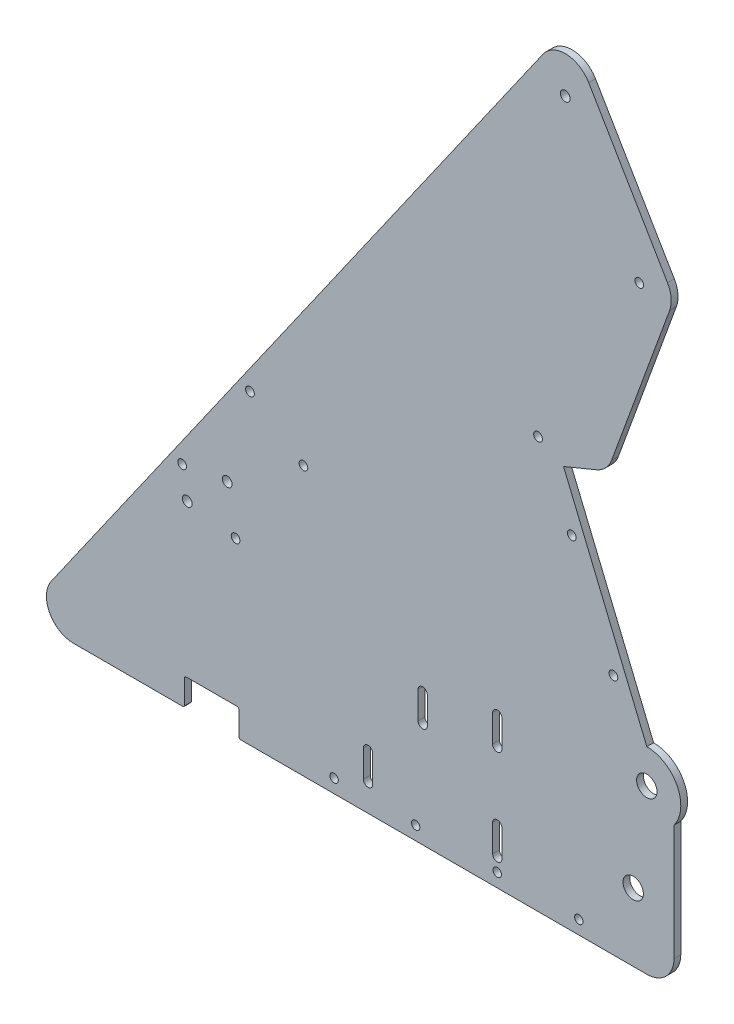
SolidWorks part; units mm, degrees
other "Markup1"
sketch "Sketch5"
ref_plane "Front Plane" through (0, 0, 0) normal (0, 0, 1) x (1, 0, 0)
ref_plane "Top Plane" through (0, 0, 0) normal (0, 1, 0) x (1, 0, 0)
ref_plane "Right Plane" through (0, 0, 0) normal (1, 0, 0) x (0, 0, -1)
sketch "Sketch1" plane through (0, 0, 0) normal (0, 0, 1) x (1, 0, 0)
  line L0 (0, 0) -> (76.2, 0)
  line L1 (304.8, 0) -> (304.8, 66.675)
  line L2 (254.9547, 364.1131) -> (0, 0)
  line L3 (304.8, 279.4) -> (254.9547, 364.1131)
  line L4 (76.2, 0) -> (76.2, 12.7)
  line L5 (76.2, 12.7) -> (101.6, 12.7)
  line L6 (101.6, 12.7) -> (101.6, 0)
  line L7 (101.6, 0) -> (304.8, 0)
  line L9 (292.1, 92.075) -> (253.2194, 185.9412)
  line L10 (253.2194, 185.9412) -> (273.7526, 194.4463)
  line L11 (273.7526, 194.4463) -> (304.8, 279.4)
  arc A0 (304.8, 66.675) -> (292.1, 92.075) centre (292.1, 76.2) ccw
  dimension "D7" = 12.7
  dimension "D8" = 76.2
  dimension "D10" = 31.75
  dimension "D1" = 304.8
  dimension "D2" = 279.4
  dimension "D3" = 55
  dimension "D4" = 444.5
  dimension "D5" = 76.2
  dimension "D6" = 25.4
  dimension "D9" = 292.1
  dimension "D11" = 101.6
  dimension "D12" = 22.5
  dimension "D13" = 22.225
extrude "Boss-Extrude1" add sketch "Sketch1" along normal blind 3.175
sketch "Sketch2" plane through (0, 0, 3.175) normal (0, 0, 1) x (1, 0, 0)
  line L0 (254.9547, 364.1131) -> (0, 0) construction
  line L1 (101.6, 0) -> (304.8, 0) construction
  line L2 (292.1, 92.075) -> (253.2194, 185.9412) construction
  line L3 (253.2194, 185.9412) -> (273.7526, 194.4463) construction
  line L4 (292.1, 92.075) -> (253.2194, 185.9412) construction
  line L5 (304.8, 279.4) -> (288.6002, 277.9261) construction
  line L6 (285.4785, 312.2373) -> (291.7219, 243.6149) construction
  line L7 (304.8, 279.4) -> (254.9547, 364.1131) construction
  line L8 (273.7526, 194.4463) -> (304.8, 279.4) construction
  line L9 (273.7526, 194.4463) -> (304.8, 279.4) construction
  circle A0 centre (77.4583, 84.0518) radius 2.286
  circle A1 centre (254, 336.1795) radius 2.286
  circle A2 centre (96.1158, 101.2872) radius 2.286
  circle A3 centre (257.0729, 160.0446) radius 2.032
  circle A4 centre (292.1, 76.2) radius 4.7625
  circle A5 centre (184.15, 6.35) radius 1.9682
  circle A6 centre (222.25, 6.35) radius 1.9682
  circle A7 centre (260.35, 6.35) radius 1.9682
  circle A8 centre (276.5132, 113.1115) radius 2.032
  circle A18 centre (288.6002, 277.9261) radius 2.032
  circle A26 centre (285.75, 31.75) radius 4.7625
  circle A28 centre (106.7599, 143.0587) radius 2.032
  circle A29 centre (106.7599, 143.0587) radius 2.032
  arc A30 (304.8, 66.675) -> (292.1, 92.075) centre (292.1, 76.2) ccw construction
  circle A31 centre (241.3, 192.0875) radius 2.032
  circle A34 centre (75.0727, 97.8047) radius 2.032
  circle A35 centre (75.0727, 97.8047) radius 2.032
  circle A37 centre (100.0405, 80.3221) radius 2.032
  circle A38 centre (100.0405, 80.3221) radius 2.032
  circle A39 centre (131.7277, 125.5761) radius 2.032
  circle A40 centre (131.7277, 125.5761) radius 2.032
  circle A41 centre (146.05, 6.35) radius 1.9682
  point P60 (288.6002, 277.9261)
  dimension "D3" = 4.572
  dimension "D5" = 4.572
  dimension "D9" = 4.572
  dimension "D14" = 3.9364
  dimension "D20" = 9.525
  dimension "D23" = 9.525
  dimension "D18" = 4.064
  dimension "D26" = 4.064
  dimension "D2" = 15.24
  dimension "D4" = 254
  dimension "D6" = 15.24
  dimension "D7" = 25.4
  dimension "D8" = 20.6375
  dimension "D15" = 146.05
  dimension "D16" = 6.35
  dimension "D21" = 44.45
  dimension "D22" = 6.35
  dimension "D19" = 160.3375
  dimension "D24" = 44.45
  dimension "D25" = 6.35
  dimension "D27" = 25.4
  dimension "D28" = 50.8
  dimension "D29" = 6.35
  dimension "D30" = 38.1
  dimension "D31" = 38.1
  dimension "D32" = 114.3
  dimension "D10" = 0.127
  dimension "D12" = 0.127
  dimension "D13" = 0.127
  dimension "D11" = 0.127
  dimension "D17" = 4
extrude "Cut-Extrude1" cut sketch "Sketch2" against normal through all
fillet "Fillet1" radius 12.7 5 edges at (0, 0, 1.5875) (304.8, 0, 1.5875) (254.9547, 364.1131, 1.5875) (273.7526, 194.4463, 1.5875) (304.8, 279.4, 1.5875)
fillet "Fillet2" radius 0.7937 4 edges at (101.6, 0, 1.5875) (101.6, 12.7, 1.5875) (76.2, 0, 1.5875) (76.2, 12.7, 1.5875)
sketch "Sketch7" plane through (0, 0, 3.175) normal (0, 0, 1) x (1, 0, 0)
  line L0 (222.25, 12.7) -> (222.25, 25.4) construction
  line L1 (220.091, 12.7) -> (220.091, 25.4)
  line L2 (224.409, 12.7) -> (224.409, 25.4)
  line L3 (222.25, 57.15) -> (222.25, 69.85) construction
  line L4 (220.091, 57.15) -> (220.091, 69.85)
  line L5 (224.409, 57.15) -> (224.409, 69.85)
  line L6 (161.925, 12.7) -> (161.925, 25.4) construction
  line L9 (187.4205, 49.1113) -> (187.4205, 61.8113) construction
  line L10 (185.2615, 49.1113) -> (185.2615, 61.8113)
  line L11 (189.5795, 49.1113) -> (189.5795, 61.8113)
  line L12 (304.8, 12.7) -> (304.8, 66.675) construction
  line L13 (102.3937, 0) -> (292.1, 0) construction
  line L14 (159.766, 12.7) -> (159.766, 25.4)
  line L15 (164.084, 12.7) -> (164.084, 25.4)
  line L16 (161.925, 25.4) -> (187.4205, 61.8113) construction
  line L17 (179.982, 60.9194) -> (167.4106, 42.9656) construction
  arc A0 (220.091, 12.7) -> (224.409, 12.7) centre (222.25, 12.7) ccw
  arc A1 (224.409, 25.4) -> (220.091, 25.4) centre (222.25, 25.4) ccw
  arc A2 (220.091, 57.15) -> (224.409, 57.15) centre (222.25, 57.15) ccw
  arc A3 (224.409, 69.85) -> (220.091, 69.85) centre (222.25, 69.85) ccw
  arc A6 (185.2615, 49.1113) -> (189.5795, 49.1113) centre (187.4205, 49.1113) ccw
  arc A7 (189.5795, 61.8113) -> (185.2615, 61.8113) centre (187.4205, 61.8113) ccw
  arc A13 (159.766, 12.7) -> (164.084, 12.7) centre (161.925, 12.7) ccw
  arc A14 (164.084, 25.4) -> (159.766, 25.4) centre (161.925, 25.4) ccw
  point P2 (222.25, 19.05)
  point P9 (222.25, 63.5)
  point P16 (161.925, 19.05)
  point P21 (187.4205, 55.4613)
  dimension "D1" = 4.318
  dimension "D2" = 12.7
  dimension "D3" = 12.7
  dimension "D4" = 44.45
  dimension "D5" = 44.45
  dimension "D7" = 82.55
  dimension "D8" = 12.7
  dimension "D9" = 60.325
extrude "Cut-Extrude2" cut sketch "Sketch7" against normal through all
equation "\"D6@Sketch2\"=\"D2@Sketch2\""
